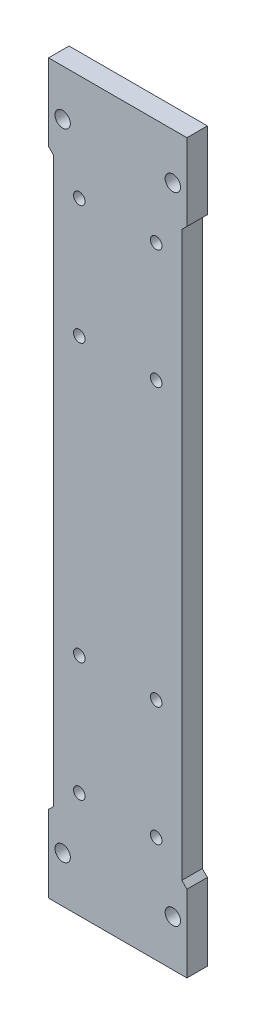
SolidWorks part; units mm, degrees
ref_plane "Front" through (0, 0, 0) normal (0, 0, 1) x (1, 0, 0)
ref_plane "Top" through (0, 0, 0) normal (0, 1, 0) x (1, 0, 0)
ref_plane "Right" through (0, 0, 0) normal (1, 0, 0) x (0, 0, -1)
sketch "Esquisse1" plane through (0, 0, 0) normal (0, 0, 1) x (1, 0, 0)
  line L1 (0, 0) -> (50, 0)
  line L2 (0, 0) -> (0, 284)
  line L3 (0, 284) -> (50, 284)
  line L4 (50, 0) -> (50, 284)
  dimension "D1" = 50
  dimension "D2" = 284
extrude "Boss.-Extru.1" add sketch "Esquisse1" along normal blind 8
sketch "Esquisse2" plane through (0, 0, 8) normal (0, 0, 1) x (1, 0, 0)
  line L0 (25, 284) -> (25, 0) construction
  line L1 (50, 284) -> (0, 284) construction
  line L2 (0, 0) -> (50, 0) construction
  line L3 (25, 142) -> (0, 142) construction
  line L4 (0, 284) -> (0, 0) construction
  circle A0 centre (3.5, 18) radius 3
  circle A1 centre (46.5, 18) radius 3
  circle A2 centre (46.5, 266) radius 3
  circle A3 centre (3.5, 266) radius 3
  dimension "D2" = 43
  dimension "D3" = 6
  dimension "D1" = 248
extrude "Enlèv. mat.-Extru.1" cut sketch "Esquisse2" against normal through all
sketch "Esquisse3" plane through (0, 0, 8) normal (0, 0, 1) x (1, 0, 0)
  line L0 (25, 284) -> (25, 0) construction
  line L1 (50, 284) -> (0, 284) construction
  line L2 (0, 0) -> (50, 0) construction
  line L3 (0, 0) -> (0, 30)
  line L4 (0, 284) -> (0, 0) construction
  line L5 (0, 30) -> (-2, 30)
  line L6 (-2, 30) -> (-2, 0)
  line L7 (-2, 0) -> (0, 0)
  line L8 (52, 0) -> (50, 0)
  line L9 (52, 30) -> (52, 0)
  line L10 (50, 30) -> (52, 30)
  line L11 (50, 0) -> (50, 30)
  line L12 (25, 142) -> (0, 142) construction
  line L13 (50, 284) -> (50, 254)
  line L14 (50, 254) -> (52, 254)
  line L15 (52, 254) -> (52, 284)
  line L16 (52, 284) -> (50, 284)
  line L17 (-2, 284) -> (0, 284)
  line L18 (-2, 254) -> (-2, 284)
  line L19 (0, 254) -> (-2, 254)
  line L20 (0, 284) -> (0, 254)
  dimension "D1" = 2
  dimension "D2" = 30
extrude "Boss.-Extru.2" add sketch "Esquisse3" against normal up to vertex (8 mm away) up to point (50, 284, 0)
chamfer "Chanfrein1" distance 2 angle 45 4 edges at (50, 30, 4) (0, 30, 4) (0, 254, 4) (50, 254, 4)
sketch "Esquisse4" plane through (0, 0, 8) normal (0, 0, 1) x (1, 0, 0)
  line L0 (0, 142) -> (50, 142) construction
  line L1 (0, 252) -> (0, 32) construction
  line L2 (50, 32) -> (50, 252) construction
  line L3 (0, 88) -> (50, 88) construction
  line L4 (0, 41.5) -> (50, 41.5) construction
  line L5 (25, 142) -> (25, 41.5) construction
  line L6 (10, 88) -> (10, 41.5) construction
  line L7 (40, 88) -> (40, 41.5) construction
  line L8 (40, 196) -> (40, 242.5) construction
  line L9 (10, 196) -> (10, 242.5) construction
  circle A0 centre (10, 41.5) radius 2.25
  circle A1 centre (10, 88) radius 2.25
  circle A2 centre (40, 88) radius 2.25
  circle A3 centre (40, 41.5) radius 2.25
  circle A4 centre (40, 242.5) radius 2.25
  circle A5 centre (40, 196) radius 2.25
  circle A6 centre (10, 196) radius 2.25
  circle A7 centre (10, 242.5) radius 2.25
  dimension "D1" = 4.5
  dimension "D2" = 30
  dimension "D3" = 100.5
  dimension "D4" = 54
extrude "Enlèv. mat.-Extru.2" cut sketch "Esquisse4" against normal through all
